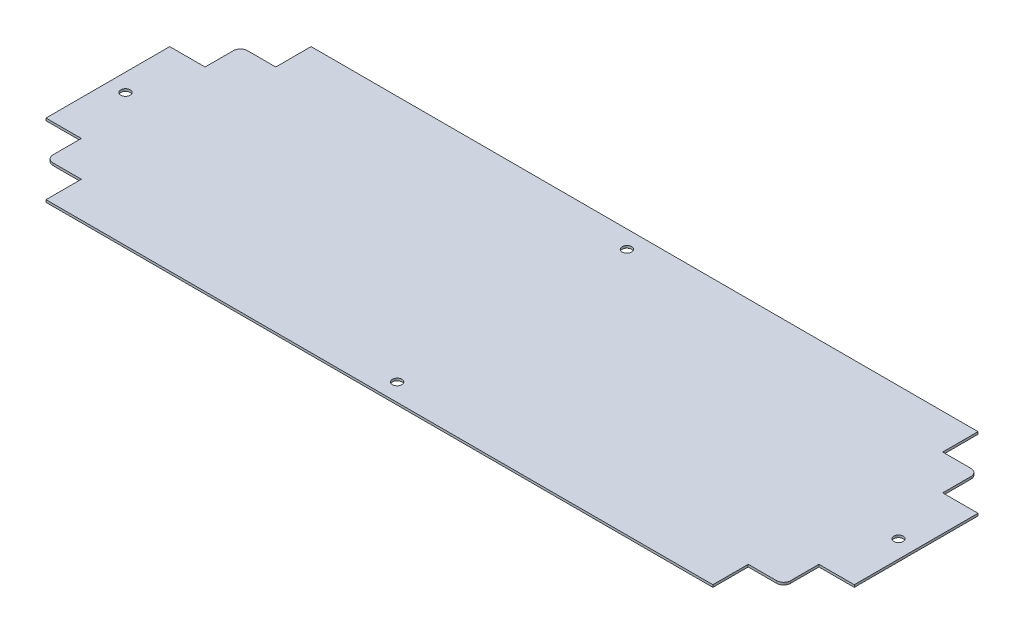
SolidWorks part; units mm, degrees
ref_plane "Front Plane" through (0, 0, 0) normal (0, 0, 1) x (1, 0, 0)
ref_plane "Top Plane" through (0, 0, 0) normal (0, 1, 0) x (1, 0, 0)
ref_plane "Right Plane" through (0, 0, 0) normal (1, 0, 0) x (0, 0, -1)
sketch "Sketch1" plane through (0, 0, 0) normal (0, 1, 0) x (1, 0, 0)
  line L1 (-156.5, 41.25) -> (156.5, 41.25) construction
  line L2 (-156.5, 41.25) -> (-156.5, -41.25) construction
  line L3 (-156.5, -41.25) -> (156.5, -41.25) construction
  line L4 (156.5, 41.25) -> (156.5, -41.25) construction
  line L5 (-156.5, 41.25) -> (156.5, -41.25) construction
  line L6 (-156.5, -41.25) -> (156.5, 41.25) construction
  line L19 (153.5, -38.25) -> (-153.5, -38.25) construction
  line L20 (153.5, -38.25) -> (153.5, 38.25) construction
  line L21 (153.5, 38.25) -> (-153.5, 38.25) construction
  line L22 (-153.5, -38.25) -> (-153.5, 38.25) construction
  line L23 (153.5, -38.25) -> (-153.5, 38.25) construction
  line L24 (153.5, 38.25) -> (-153.5, -38.25) construction
  line L25 (141.5, 56.25) -> (-141.5, 56.25)
  line L28 (-171.5, 26.25) -> (-171.5, -26.25)
  line L31 (-141.5, -56.25) -> (141.5, -56.25)
  line L34 (171.5, -26.25) -> (171.5, 26.25)
  line L36 (-156.5, 0) -> (-171.5, 0) construction
  line L37 (156.5, 0) -> (171.5, 0) construction
  line L38 (-156.5, 38.25) -> (-153.5, 38.25) construction
  line L43 (0, 56.25) -> (0, 41.25) construction
  line L44 (0, -56.25) -> (0, -41.25) construction
  line L45 (-153.5, 38.25) -> (-153.5, 41.25) construction
  line L46 (-153.5, -41.25) -> (-153.5, -38.25) construction
  line L47 (-153.5, -38.25) -> (-156.5, -38.25) construction
  line L48 (153.5, -41.25) -> (153.5, -38.25) construction
  line L49 (153.5, -38.25) -> (156.5, -38.25) construction
  line L50 (153.5, 38.25) -> (153.5, 41.25) construction
  line L51 (156.5, 38.25) -> (153.5, 38.25) construction
  line L52 (-141.5, 56.25) -> (-141.5, 41.25)
  line L53 (-141.5, 41.25) -> (-153.5, 41.25)
  line L54 (-171.5, 26.25) -> (-156.5, 26.25)
  line L55 (-156.5, 26.25) -> (-156.5, 38.25)
  line L56 (-171.5, -26.25) -> (-156.5, -26.25)
  line L57 (-156.5, -26.25) -> (-156.5, -38.25)
  line L58 (-141.5, -56.25) -> (-141.5, -41.25)
  line L59 (-141.5, -41.25) -> (-153.5, -41.25)
  line L60 (141.5, -56.25) -> (141.5, -41.25)
  line L61 (141.5, -41.25) -> (153.5, -41.25)
  line L62 (171.5, -26.25) -> (156.5, -26.25)
  line L63 (156.5, -26.25) -> (156.5, -38.25)
  line L64 (171.5, 26.25) -> (156.5, 26.25)
  line L65 (156.5, 26.25) -> (156.5, 38.25)
  line L66 (141.5, 56.25) -> (141.5, 41.25)
  line L67 (141.5, 41.25) -> (153.5, 41.25)
  arc A0 (-153.5, 41.25) -> (-156.5, 38.25) centre (-153.5, 38.25) ccw
  arc A1 (-156.5, -38.25) -> (-153.5, -41.25) centre (-153.5, -38.25) ccw
  arc A2 (153.5, -41.25) -> (156.5, -38.25) centre (153.5, -38.25) ccw
  arc A3 (153.5, 41.25) -> (156.5, 38.25) centre (153.5, 38.25) cw
  circle A4 centre (0, 48.75) radius 2
  circle A5 centre (0, -48.75) radius 2
  circle A6 centre (-164, 0) radius 2
  circle A7 centre (164, 0) radius 2
  point P0 (0, 0)
  point P5 (0, 0)
  point P31 (0, 0)
  point P52 (0, -41.25)
  point P53 (3.4253, -48.75)
  point P54 (5.1007, -56.25)
  point P55 (-3.2799, -56.25)
  dimension "D5" = 15
  dimension "D9" = 4
  dimension "D11" = 15
  dimension "D1" = 82.5
  dimension "D2" = 313
  dimension "D3" = 15
  dimension "D4" = 3
  dimension "D6" = 15
  dimension "D7" = 15
  dimension "D8" = 15
  dimension "D10" = 15
  dimension "D12" = 15
extrude "Boss-Extrude1" add sketch "Sketch1" along normal blind 1
